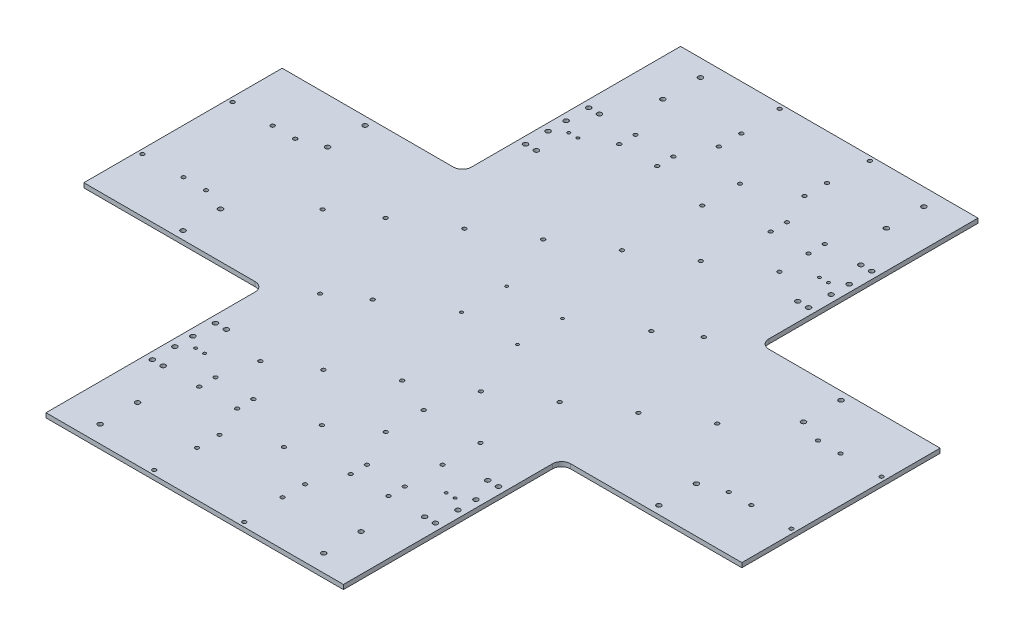
SolidWorks part; units mm, degrees
material "3.0205 (EN-AW 1200)"
ref_plane "前视基准面" through (0, 0, 0) normal (0, 0, 1) x (1, 0, 0)
ref_plane "上视基准面" through (0, 0, 0) normal (0, 1, 0) x (1, 0, 0)
ref_plane "右视基准面" through (0, 0, 0) normal (1, 0, 0) x (0, 0, -1)
other "Configuration Table"
sketch "Sketch1" plane through (0, 0, 0) normal (0, 1, 0) x (1, 0, 0)
  line L0 (165, 352) -> (-165, 352)
  line L1 (-165, 352) -> (-165, 110)
  line L2 (-165, 110) -> (-365, 110)
  line L5 (-365, 110) -> (-365, -110)
  line L6 (0, 352) -> (0, -66.8675) construction
  line L7 (-365, 0) -> (131.0517, 0) construction
  line L8 (365, 110) -> (365, -110)
  line L11 (165, 110) -> (365, 110)
  line L12 (165, 352) -> (165, 110)
  line L13 (165, -352) -> (165, -110)
  line L14 (165, -110) -> (365, -110)
  line L19 (-165, -110) -> (-365, -110)
  line L20 (-165, -352) -> (-165, -110)
  line L21 (165, -352) -> (-165, -352)
  point P21 (365, 0)
  dimension "D1" = 165
  dimension "D2" = 200
  dimension "D3" = 110
  dimension "D4" = 242
extrude "Boss-Extrude1" add sketch "Sketch1" along normal blind 5
sketch "Sketch2" plane through (0, 5, 0) normal (0, 1, 0) x (1, 0, 0)
  line L2 (365, 110) -> (165, 110) construction
  line L3 (365, -110) -> (365, 110) construction
  line L4 (-56.7455, 0) -> (47.5165, 0) construction
  line L5 (0, 54.7142) -> (0, -64.2255) construction
  line L7 (165, 352) -> (-165, 352) construction
  circle A0 centre (315, 49.5) radius 2.125
  circle A1 centre (290, 49.5) radius 2.125
  circle A7 centre (290, -49.5) radius 2.125
  circle A8 centre (315, -49.5) radius 2.125
  circle A9 centre (-315, -49.5) radius 2.125
  circle A10 centre (-290, -49.5) radius 2.125
  circle A13 centre (-290, 49.5) radius 2.125
  circle A14 centre (-315, 49.5) radius 2.125
  circle A15 centre (47.5, 302) radius 2.125
  circle A16 centre (47.5, 277) radius 2.125
  circle A17 centre (-47.5, 277) radius 2.125
  circle A18 centre (-47.5, 302) radius 2.125
  circle A19 centre (-47.5, -302) radius 2.125
  circle A20 centre (-47.5, -277) radius 2.125
  circle A21 centre (47.5, -277) radius 2.125
  circle A22 centre (47.5, -302) radius 2.125
  dimension "D1" = 60.5
  dimension "D5" = 4.25
  dimension "D7" = 4.25
  dimension "D9" = 4.25
  dimension "D10" = 4.25
  dimension "D4" = 25
  dimension "D6" = 50
  dimension "D11" = 47.5
  dimension "D12" = 50
  dimension "D13" = 25
extrude "Cut-Extrude1" cut sketch "Sketch2" against normal blind 3
sketch "Sketch4" plane through (0, 5, 0) normal (0, 1, 0) x (1, 0, 0)
  line L0 (-165, 352) -> (-165, 110) construction
  line L1 (165, 352) -> (-165, 352) construction
  line L2 (0, 46.9886) -> (0, -40.2904) construction
  line L3 (-35.103, 0) -> (92.4951, 0) construction
  line L5 (165, -352) -> (165, -110) construction
  circle A0 centre (-157, 172) radius 2.6
  circle A1 centre (-145, 172) radius 2.6
  circle A2 centre (-157, 197) radius 2.6
  circle A3 centre (-157, 217) radius 2.6
  circle A4 centre (-157, 242) radius 2.6
  circle A5 centre (-145, 242) radius 2.6
  circle A6 centre (145, 242) radius 2.6
  circle A7 centre (157, 242) radius 2.6
  circle A8 centre (157, 217) radius 2.6
  circle A9 centre (157, 197) radius 2.6
  circle A10 centre (145, 172) radius 2.6
  circle A11 centre (157, 172) radius 2.6
  circle A12 centre (157, -172) radius 2.6
  circle A13 centre (145, -172) radius 2.6
  circle A14 centre (157, -197) radius 2.6
  circle A15 centre (157, -217) radius 2.6
  circle A16 centre (157, -242) radius 2.6
  circle A17 centre (145, -242) radius 2.6
  circle A18 centre (-145, -242) radius 2.6
  circle A19 centre (-157, -242) radius 2.6
  circle A20 centre (-157, -217) radius 2.6
  circle A21 centre (-157, -197) radius 2.6
  circle A22 centre (-145, -172) radius 2.6
  circle A23 centre (-157, -172) radius 2.6
  circle A24 centre (144, -207) radius 1.6
  circle A25 centre (-144, -207) radius 1.6
  circle A26 centre (144, 207) radius 1.6
  circle A27 centre (-144, 207) radius 1.6
  circle A28 centre (134, -207) radius 1.6
  circle A29 centre (-134, -207) radius 1.6
  circle A30 centre (134, 207) radius 1.6
  circle A31 centre (-134, 207) radius 1.6
  dimension "D3" = 5.2
  dimension "D4" = 5.2
  dimension "D5" = 8
  dimension "D6" = 8
  dimension "D9" = 5.2
  dimension "D10" = 5.2
  dimension "D11" = 5.2
  dimension "D12" = 5.2
  dimension "D19" = 3.2
  dimension "D20" = 21
  dimension "D21" = 10
  dimension "D22" = 3.2
  dimension "D23" = 10
  dimension "D1" = 8
  dimension "D2" = 20
  dimension "D7" = 8
  dimension "D8" = 20
  dimension "D13" = 25
  dimension "D14" = 20
  dimension "D15" = 25
  dimension "D16" = 25
  dimension "D17" = 110
  dimension "D18" = 0
extrude "Cut-Extrude3" cut sketch "Sketch4" against normal blind 10
sketch "Sketch5" plane through (0, 5, 0) normal (0, 1, 0) x (1, 0, 0)
  line L0 (165, 352) -> (-165, 352) construction
  line L5 (-46.9195, 0) -> (66.6223, 0) construction
  line L6 (0, 59.0569) -> (0, -54.4849) construction
  line L10 (-365, 110) -> (-365, -110) construction
  line L12 (-165, 110) -> (-365, 110) construction
  line L13 (-365, -110) -> (-165, -110) construction
  circle A0 centre (-50, 347) radius 2.125
  circle A1 centre (50, 347) radius 2.125
  circle A2 centre (50, -347) radius 2.125
  circle A3 centre (-50, -347) radius 2.125
  circle A4 centre (-360, 50) radius 2.125
  circle A5 centre (-360, -50) radius 2.125
  circle A6 centre (360, -50) radius 2.125
  circle A7 centre (360, 50) radius 2.125
  dimension "D1" = 4.25
  dimension "D2" = 4.25
  dimension "D3" = 60
  dimension "D6" = 4.25
  dimension "D7" = 4.25
  dimension "5" = 5
  dimension "D4" = 50
  dimension "D5" = 50
  dimension "D8" = 60
  dimension "D9" = 5
  dimension "D10" = 5
extrude "Cut-Extrude4" cut sketch "Sketch5" against normal blind 10
fillet "Fillet1" radius 10 4 edges at (-165, 2.5, -110) (-165, 2.5, 110) (165, 2.5, 110) (165, 2.5, -110)
sketch "Sketch6" plane through (0, 5, 0) normal (0, 1, 0) x (1, 0, 0)
  line L0 (165, 352) -> (-165, 352) construction
  line L2 (165, 120) -> (165, 352) construction
  line L3 (-64.416, 0) -> (103.2752, 0) construction
  line L4 (0, 86.0771) -> (0, -73.7041) construction
  line L5 (365, 110) -> (175, 110) construction
  line L6 (365, -110) -> (365, 110) construction
  circle A0 centre (124, 333) radius 2.6
  circle A1 centre (124, 291.4) radius 2.6
  circle A2 centre (124, -291.4) radius 2.6
  circle A3 centre (124, -333) radius 2.6
  circle A4 centre (-124, -333) radius 2.6
  circle A5 centre (-124, -291.4) radius 2.6
  circle A6 centre (-124, 291.4) radius 2.6
  circle A7 centre (-124, 333) radius 2.6
  circle A8 centre (264, 101) radius 2.6
  circle A9 centre (264, 59.4) radius 2.6
  circle A10 centre (264, -59.4) radius 2.6
  circle A11 centre (264, -101) radius 2.6
  circle A12 centre (-264, -101) radius 2.6
  circle A13 centre (-264, -59.4) radius 2.6
  circle A14 centre (-264, 59.4) radius 2.6
  circle A15 centre (-264, 101) radius 2.6
  dimension "D1" = 5.2
  dimension "D2" = 5.2
  dimension "D6" = 5.2
  dimension "D7" = 5.2
  dimension "D3" = 19
  dimension "D4" = 41
  dimension "D5" = 41.6
  dimension "D8" = 9
  dimension "D9" = 41.6
  dimension "D10" = 101
extrude "Cut-Extrude5" cut sketch "Sketch6" against normal blind 10
sketch "Sketch7" plane through (0, 5, 0) normal (0, 1, 0) x (1, 0, 0)
  line L0 (197.463, 121.9013) -> (-168.3949, -103.9565) construction
  line L1 (180, 235.6925) -> (-379.973, -110) construction
  line L2 (144.6063, 226.5583) -> (333.7962, -79.9026) construction
  line L3 (-55.682, 90.1971) -> (55.682, -90.1971) construction
  line L4 (-167.9289, -112.9289) -> (167.9289, 112.9289) construction
  circle A0 centre (-55.682, 90.1971) radius 2.125
  circle A1 centre (-1.6489, 123.5538) radius 2.125
  circle A2 centre (52.3842, 156.9105) radius 2.125
  circle A3 centre (106.4174, 190.2672) radius 2.125
  circle A4 centre (-109.7152, 56.8404) radius 2.125
  circle A5 centre (-163.7483, 23.4837) radius 2.125
  circle A6 centre (-206.9749, -3.2017) radius 2.125
  circle A7 centre (-95.6108, -183.5958) radius 2.125
  circle A8 centre (-52.3842, -156.9105) radius 2.125
  circle A9 centre (1.6489, -123.5538) radius 2.125
  circle A10 centre (217.7815, 9.873) radius 2.125
  circle A11 centre (163.7483, -23.4837) radius 2.125
  circle A12 centre (109.7152, -56.8404) radius 2.125
  circle A13 centre (55.682, -90.1971) radius 2.125
  arc A14 (165, 120) -> (175, 110) centre (175, 120) ccw construction
  arc A15 (-165, -120) -> (-175, -110) centre (-175, -120) ccw construction
  point P35 (0, 0)
  point P36 (167.9289, 112.9289)
  point P37 (-167.9289, -112.9289)
  dimension "D1" = 4.25
  dimension "D2" = 4.25
  dimension "D3" = 4.25
  dimension "4.25" = 4.25
  dimension "D5" = 4.25
  dimension "D6" = 4.25
  dimension "D7" = 4.25
  dimension "D8" = 63.5
  dimension "D9" = 63.5
  dimension "D10" = 50.8
  dimension "D11" = 63.5
  dimension "D12" = 63.5
  dimension "D13" = 63.5
  dimension "D14" = 0
  dimension "D15" = 0
  dimension "D16" = 106
extrude "Cut-Extrude6" cut sketch "Sketch7" against normal blind 10
sketch "Sketch8" plane through (0, 5, 0) normal (0, 1, 0) x (1, 0, 0)
  line L0 (167.9289, 112.9289) -> (-167.9289, -112.9289) construction
  line L1 (81.1937, 116.467) -> (145.4556, 20.9075) construction
  line L2 (-135.7714, -35.3081) -> (-80.5576, -117.413) construction
  line L3 (0, 77.1364) -> (0, -65.7088) construction
  line L4 (-60.3124, 0) -> (69.2005, 0) construction
  line L5 (165, 352) -> (-165, 352) construction
  arc A0 (165, 120) -> (175, 110) centre (175, 120) ccw construction
  arc A1 (-165, -120) -> (-175, -110) centre (-175, -120) ccw construction
  circle A2 centre (-127.2679, -85.5852) radius 2.1
  circle A3 centre (-92.4156, -62.1477) radius 2.1
  circle A4 centre (92.4156, 62.1477) radius 2.1
  circle A5 centre (127.2679, 85.5852) radius 2.1
  circle A6 centre (0, 253) radius 2.1
  circle A7 centre (0, 211) radius 2.1
  circle A8 centre (0, -211) radius 2.1
  circle A9 centre (0, -253) radius 2.1
  dimension "D3" = 4.2
  dimension "D4" = 4.2
  dimension "D5" = 4.2
  dimension "D6" = 4.2
  dimension "D8" = 21
  dimension "D11" = 4.2
  dimension "D12" = 4.2
  dimension "D1" = 70
  dimension "D2" = 70
  dimension "D7" = 21
  dimension "D9" = 21
  dimension "D10" = 21
  dimension "D13" = 99
  dimension "D14" = 42
extrude "Cut-Extrude7" cut sketch "Sketch8" against normal blind 10
sketch "Sketch9" plane through (0, 5, 0) normal (0, 1, 0) x (1, 0, 0)
  line L0 (0, 50.376) -> (0, -37.6511) construction
  line L1 (-100.5221, 0) -> (79.2832, 0) construction
  circle A0 centre (-31, 25) radius 1.575
  circle A1 centre (-31, -25) radius 1.575
  circle A2 centre (31, -25) radius 1.575
  circle A3 centre (31, 25) radius 1.575
  point P9 (-27.4996, 0)
  dimension "D1" = 3.15
  dimension "D2" = 31
  dimension "D3" = 25
extrude "Cut-Extrude8" cut sketch "Sketch9" against normal blind 10
sketch "Sketch11" plane through (0, 5, 0) normal (0, 1, 0) x (1, 0, 0)
  line L0 (0, 181.8895) -> (0, -221.8861) construction
  line L1 (-154.2728, 0) -> (170.1444, 0) construction
  line L2 (165, 120) -> (165, 352) construction
  line L3 (165, 352) -> (-165, 352) construction
  circle A0 centre (63, 242) radius 2.125
  circle A1 centre (63, 224) radius 2.125
  circle A2 centre (105, 242) radius 2.125
  circle A3 centre (105, 224) radius 2.125
  circle A4 centre (-105, 224) radius 2.125
  circle A5 centre (-105, 242) radius 2.125
  circle A6 centre (-63, 224) radius 2.125
  circle A7 centre (-63, 242) radius 2.125
  circle A8 centre (-63, -242) radius 2.125
  circle A9 centre (-63, -224) radius 2.125
  circle A10 centre (-105, -242) radius 2.125
  circle A11 centre (-105, -224) radius 2.125
  circle A12 centre (105, -224) radius 2.125
  circle A13 centre (105, -242) radius 2.125
  circle A14 centre (63, -224) radius 2.125
  circle A15 centre (63, -242) radius 2.125
  dimension "D1" = 4.25
  dimension "D2" = 4.25
  dimension "D5" = 4.25
  dimension "D6" = 4.25
  dimension "D3" = 18
  dimension "D4" = 42
  dimension "D7" = 60
  dimension "D8" = 110
extrude "Cut-Extrude9" cut sketch "Sketch11" against normal blind 10
sketch "Sketch12" plane through (0, 5, 0) normal (0, 1, 0) x (1, 0, 0)
  line L0 (-165, -352) -> (165, -352) construction
  line L1 (165, -352) -> (165, -120) construction
  circle A0 centre (42, -140) radius 2.125
  circle A1 centre (105, -140) radius 2.125
  circle A2 centre (42, -182) radius 2.125
  circle A3 centre (105, -182) radius 2.125
  dimension "D3" = 4.25
  dimension "D4" = 4.25
  dimension "D5" = 4.25
  dimension "D6" = 4.25
  dimension "D1" = 63
  dimension "D2" = 42
  dimension "D7" = 170
  dimension "D8" = 60
extrude "Cut-Extrude10" cut sketch "Sketch12" against normal blind 10
